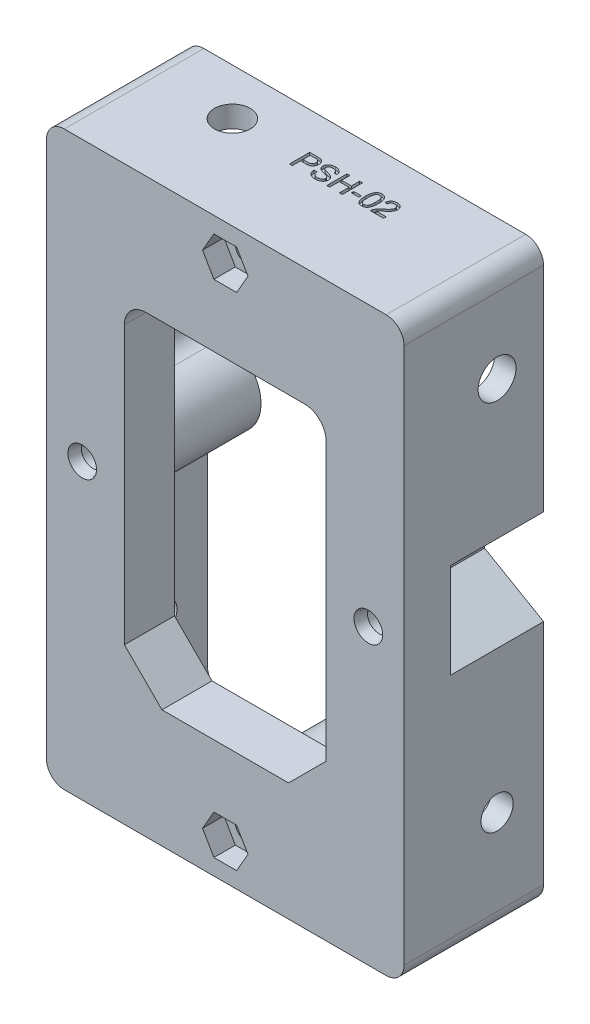
SolidWorks part; units mm, degrees
ref_plane "Front" through (0, 0, 0) normal (0, 0, 1) x (1, 0, 0)
ref_plane "Top" through (0, 0, 0) normal (0, 1, 0) x (1, 0, 0)
ref_plane "Right" through (0, 0, 0) normal (1, 0, 0) x (0, 0, -1)
sketch "Sketch3" plane through (0, 0, 0) normal (0, 0, 1) x (1, 0, 0)
  line L0 (10.9, 16.5) -> (0, 16.5) construction
  line L1 (0, 0) -> (50, 0)
  line L2 (0, 0) -> (0, 80)
  line L3 (0, 80) -> (50, 80)
  line L4 (50, 0) -> (50, 80)
  line L5 (10.9, 16.5) -> (39.1, 16.5)
  line L6 (10.9, 16.5) -> (10.9, 63.5)
  line L7 (10.9, 63.5) -> (39.1, 63.5)
  line L8 (39.1, 16.5) -> (39.1, 63.5)
  line L9 (39.1, 16.5) -> (50, 16.5) construction
  line L10 (10.9, 16.5) -> (10.9, 0) construction
  line L11 (10.9, 63.5) -> (10.9, 80) construction
  line L12 (25, 80) -> (25, 75) construction
  line L13 (25, 0) -> (25, 5) construction
  line L14 (25, 41) -> (5, 41) construction
  line L15 (25, 41) -> (45, 41) construction
  circle A0 centre (5, 41) radius 1.6 construction
  circle A1 centre (45, 41) radius 1.6 construction
  circle A2 centre (25, 5) radius 1.6
  circle A3 centre (25, 75) radius 1.6
  point P20 (0, 0)
  point P22 (25, 63.5)
  point P27 (0, 0)
  point P28 (0, 0)
  point P29 (0, 0)
  point P30 (0, 0)
  dimension "D5" = 40
  dimension "D6" = 3.2
  dimension "D1" = 50
  dimension "D2" = 80
  dimension "D3" = 28.2
  dimension "D4" = 22.5
  dimension "D7" = 24.5
  dimension "D8" = 70
extrude "Boss-Extrude1" add sketch "Sketch3" along normal blind 19.5
sketch "Sketch17" plane through (0, 0, 19.5) normal (0, 0, 1) x (1, 0, 0)
  circle A0 centre (45, 41) radius 1.6 construction
  circle A1 centre (5, 41) radius 1.6 construction
  circle A2 centre (45, 41) radius 1.6
  circle A3 centre (5, 41) radius 1.6
extrude "Cut-Extrude7" cut sketch "Sketch17" against normal through all
chamfer "Chamfer1" distance 0.4 angle 75 2 edges at (46.6, 41, 19.5) (6.6, 41, 19.5) first distance on face at (46.6, 41, 19.5)
sketch "Sketch4" plane through (0, 0, 0) normal (0, 0, -1) x (-1, 0, 0)
  line L0 (-19.8765, 3) -> (-3, 3)
  line L1 (-30.1235, 77) -> (-47, 77)
  line L4 (-47, 35.8765) -> (-47, 3)
  line L5 (-3, 46.1235) -> (-3, 77)
  line L8 (-47, 3) -> (-3, 3)
  line L9 (-3, 3) -> (-3, 77)
  line L10 (-47, 77) -> (-47, 3)
  line L11 (-3, 77) -> (-47, 77)
  line L12 (-47, 3) -> (-30.1235, 3)
  line L13 (-3, 3) -> (-3, 35.8765)
  line L14 (-47, 77) -> (-47, 46.1235)
  line L15 (-3, 77) -> (-19.8765, 77)
  arc A0 (-47, 35.8765) -> (-47, 46.1235) centre (-45, 41) ccw
  arc A1 (-3, 46.1235) -> (-3, 35.8765) centre (-5, 41) ccw
  arc A2 (-19.8765, 3) -> (-30.1235, 3) centre (-25, 5) ccw
  arc A3 (-30.1235, 77) -> (-19.8765, 77) centre (-25, 75) ccw
  circle A4 centre (-25, 75) radius 1.6 construction
  dimension "D2" = 11
  dimension "D1" = 3
extrude "Cut-Extrude1" cut sketch "Sketch4" against normal offset from surface (12.5 mm away) 7 up to face at (43, 41, 19.5)
fillet "Fillet1" radius 2.5 4 edges at (0, 0, 9.75) (50, 0, 9.75) (50, 80, 9.75) (0, 80, 9.75)
fillet "Fillet2" radius 2.5 12 edges at (3, 35.8765, 6.25) (3, 46.1235, 6.25) (47, 35.8765, 6.25) (47, 46.1235, 6.25) (47, 3, 6.25) (3, 77, 6.25) (47, 77, 6.25) (19.8765, 77, 6.25) (30.1235, 77, 6.25) (19.8765, 3, 6.25) (30.1235, 3, 6.25) (3, 3, 6.25)
sketch "Sketch5" plane through (0, 0, 0) normal (-1, 0, 0) x (0, 0, 1)
  line L1 (0, 80) -> (19.5, 80) construction
  line L2 (6.5, 67) -> (6.5, 42) construction
  line L3 (6.5, 42) -> (6.5, 14.5) construction
  line L4 (19.5, 77.5) -> (19.5, 2.5) construction
  circle A0 centre (6.5, 67) radius 2.5
  circle A2 centre (6.5, 14.5) radius 2.25
  dimension "D1" = 13
  dimension "D2" = 5
  dimension "D3" = 13
  dimension "D4" = 25
  dimension "D5" = 14.5
  dimension "D6" = 4.5
extrude "Cut-Extrude2" cut sketch "Sketch5" against normal up to next
hole_wizard "M5 Clearance Hole1" positions "Sketch6" profile "Sketch7" hole size "M5" standard "ANSI Metric" end condition up to next
sketch "Sketch6" plane through (47, 0, 0) normal (-1, 0, 0) x (0, 0, 1)
  point P0 (6.5, 67)
sketch "Sketch7" plane through (47, 67, 6.5) normal (0, 1, 0) x (0, 0, 1)
  line L0 (0, 0) -> (0, 3)
  line L1 (0, 3) -> (2.65, 3)
  line L2 (2.65, 3) -> (2.65, 0)
  line L5 (2.65, 0) -> (0, 0)
  line L11 (0, -6.35) -> (0, 107.95) construction
  dimension "Thru Hole Dia." = 5.3
  dimension "Thru Hole Depth" = 3
sketch "Sketch8" plane through (0, 80, 0) normal (0, 1, 0) x (1, 0, 0)
  line L1 (0, -19.5) -> (0, 0) construction
  line L2 (47.5, -19.5) -> (2.5, -19.5) construction
  circle A0 centre (13, -6.5) radius 2.5
  dimension "D1" = 5
  dimension "D3" = 13
  dimension "D2" = 13
extrude "Cut-Extrude3" cut sketch "Sketch8" against normal up to surface (77 mm away) up to face at (38.7422, 3, 6.25)
hole_wizard "M5 Clearance Hole2" positions "Sketch10" profile "Sketch11" hole size "M5" standard "ANSI Metric" end condition up to next
sketch "Sketch10" plane through (0, 3, 0) normal (0, 1, 0) x (1, 0, 0)
  point P0 (13, -6.5)
sketch "Sketch11" plane through (13, 3, 6.5) normal (1, 0, 0) x (0, 0, 1)
  line L0 (0, 0) -> (0, 3)
  line L1 (0, 3) -> (2.65, 3)
  line L2 (2.65, 3) -> (2.65, 0)
  line L5 (2.65, 0) -> (0, 0)
  line L11 (0, -6.35) -> (0, 107.95) construction
  dimension "Thru Hole Dia." = 5.3
  dimension "Thru Hole Depth" = 3
sketch "Sketch12" plane through (47, 0, 0) normal (-1, 0, 0) x (0, 0, 1)
  circle A0 centre (6.5, 14.5) radius 2.25 construction
  circle A1 centre (6.5, 14.5) radius 2.25
extrude "Cut-Extrude4" cut sketch "Sketch12" against normal through all
sketch "Sketch13" plane through (0, 80, 0) normal (0, 1, 0) x (1, 0, 0)
  line L0 (8, -8) -> (50, -8) construction
  line L1 (50, 0) -> (50, -19.5) construction
  line L2 (47.5, 0) -> (2.5, 0) construction
  text T0 "PSH-02"
  dimension "D1" = 8
extrude "Part Number" cut sketch "Sketch13" against normal blind 0.4
sketch "Sketch14" plane through (0, 0, 19.5) normal (0, 0, 1) x (1, 0, 0)
  line L1 (10.25, 68.5) -> (39.75, 68.5)
  line L2 (10.25, 68.5) -> (10.25, 11.5)
  line L3 (10.25, 11.5) -> (39.75, 11.5)
  line L4 (39.75, 68.5) -> (39.75, 11.5)
  line L6 (25, 68.5) -> (25, 63.5) construction
  line L7 (39.1, 63.5) -> (10.9, 63.5) construction
  line L8 (25, 11.5) -> (25, 16.5) construction
  line L9 (10.9, 16.5) -> (39.1, 16.5) construction
  dimension "D1" = 57
  dimension "D2" = 29.5
extrude "Omnicom Enlarged Socket Cavity" [suppressed] cut sketch "Sketch14" against normal through all
sketch "Sketch15" [suppressed] plane through (0, 0, 23) normal (0, 0, 1) x (1, 0, 0)
  line L0 (25, 40) -> (39.1, 40) construction
  line L1 (10, 9.5) -> (40, 9.5)
  line L2 (10, 9.5) -> (10, 70.5)
  line L3 (10, 70.5) -> (40, 70.5)
  line L4 (40, 9.5) -> (40, 70.5)
  line L5 (10, 9.5) -> (40, 70.5) construction
  line L6 (10, 70.5) -> (40, 9.5) construction
  line L7 (39.1, 16.4) -> (39.1, 63.6) construction
  line L8 (25, 40) -> (10.9, 40) construction
  line L9 (10.9, 63.6) -> (10.9, 16.4) construction
  point P0 (25, 40)
  dimension "D1" = 61
  dimension "D2" = 30
extrude "Astrodyne Enlarged Socket Cavity" [suppressed] cut sketch "Sketch15" against normal through all
sketch "Sketch16" [suppressed] plane through (0, 0, 23) normal (0, 0, 1) x (1, 0, 0)
  line L0 (25, 76) -> (25, 70.5) construction
  line L1 (40, 70.5) -> (10, 70.5) construction
  line L2 (25, 4) -> (25, 9.5) construction
  line L3 (10, 9.5) -> (40, 9.5) construction
  circle A0 centre (25, 76) radius 1.4
  circle A1 centre (25, 4) radius 1.4
  dimension "D1" = 72
  dimension "D2" = 2.8
extrude "Cut-Extrude6" [suppressed] cut sketch "Sketch16" against normal through all
chamfer "Chamfer2" [suppressed] distance 0.4 angle 70
ref_plane "Plane1" [suppressed] through (0, 0, 10) normal (0, 0, 1) x (1, 0, 0)
sketch "Sketch18" [suppressed] plane through (0, 0, 10) normal (0, 0, 1) x (1, 0, 0)
  line L0 (47, 70) -> (46.2, 70) construction
  line L1 (47, 72.65) -> (47, 67.35) construction
  line L2 (46.2, 70) -> (-6.9259, 84.235) construction
  line L3 (46.2, 70) -> (26.1844, 70) construction
  dimension "D1" = 15
  dimension "D2" = 55
  dimension "D3" = 0.8
ref_plane "Plane2" [suppressed] through (-6.9259, 84.235, 10) normal (-0.9659, 0.2588, 0) x (0, 0, 1)
sketch "Sketch19" [suppressed] plane through (-6.9259, 84.235, 10) normal (-0.9659, 0.2588, 0) x (0, 0, 1)
  line L0 (0, 0) -> (0, -5.1804) construction
  circle A0 centre (0, 0) radius 2
  dimension "D1" = 4
extrude "Cut-Extrude8" [suppressed] cut sketch "Sketch19" against normal up to surface (56.3641 mm away) up to face at (47, 67, 9.15)
chamfer "Chamfer3" distance 5.25 2 edges at (39.1, 16.5, 16) (10.9, 16.5, 16)
fillet "Fillet3" radius 3 2 edges at (39.1, 63.5, 16) (10.9, 63.5, 16)
sketch "Sketch21" plane through (0, 0, 12.5) normal (0, 0, -1) x (-1, 0, 0)
  line L1 (-42.25, 39.4123) -> (-42.25, 42.5877)
  line L2 (-42.25, 42.5877) -> (-45, 44.1754)
  line L3 (-45, 44.1754) -> (-47.75, 42.5877)
  line L4 (-47.75, 42.5877) -> (-47.75, 39.4123)
  line L5 (-47.75, 39.4123) -> (-45, 37.8246)
  line L6 (-45, 37.8246) -> (-42.25, 39.4123)
  line L7 (-7.75, 39.4123) -> (-5, 37.8246)
  line L8 (-5, 37.8246) -> (-2.25, 39.4123)
  line L9 (-2.25, 39.4123) -> (-2.25, 42.5877)
  line L10 (-2.25, 42.5877) -> (-5, 44.1754)
  line L11 (-5, 44.1754) -> (-7.75, 42.5877)
  line L12 (-7.75, 42.5877) -> (-7.75, 39.4123)
  circle A0 centre (-45, 41) radius 2.75 construction
  circle A1 centre (-5, 41) radius 2.75 construction
  dimension "D1" = 5.5
extrude "Cut-Extrude9" cut sketch "Sketch21" against normal blind 3.5 and the other way through all
sketch "Sketch23" plane through (0, 0, 0) normal (0, 0, -1) x (-1, 0, 0)
  line L0 (-42.25, 42.5877) -> (-42, 43.0207) construction
  line L4 (-45, 37.8246) -> (-42.25, 39.4123) construction
  line L5 (-42.25, 39.4123) -> (-42, 38.9793) construction
  line L6 (-50, 47.6395) -> (-50, 34.3605)
  line L7 (-42.25, 41) -> (-41.75, 41) construction
  line L8 (-42.25, 42.5877) -> (-45, 44.1754) construction
  line L9 (-42.25, 39.4123) -> (-42.25, 42.5877) construction
  line L11 (-41.75, 42.8764) -> (-50, 47.6395)
  line L12 (-41.75, 39.1236) -> (-41.75, 42.8764)
  line L13 (-50, 34.3605) -> (-41.75, 39.1236)
  line L14 (-42.25, 39.4123) -> (-42.25, 42.5877) construction
  line L15 (-50, 2.5) -> (-50, 77.5) construction
  line L17 (-25, 75) -> (-25, 5) construction
  line L18 (-7.75, 41) -> (-8.25, 41) construction
  line L21 (-7.75, 39.4123) -> (-8, 38.9793) construction
  line L22 (-7.75, 42.5877) -> (-8, 43.0207) construction
  line L23 (0, 34.3605) -> (-8.25, 39.1236)
  line L24 (-8.25, 39.1236) -> (-8.25, 42.8764)
  line L28 (-8.25, 42.8764) -> (0, 47.6395)
  line L29 (0, 47.6395) -> (0, 34.3605)
  dimension "D1" = 0.5
extrude "Cut-Extrude10" cut sketch "Sketch23" against normal offset from surface (13 mm away) 3 up to face at (45, 41, 16)
fillet "Fillet5" [suppressed] radius 2
chamfer "Chamfer5" [suppressed] distance 2 angle 45
sketch "Sketch24" plane through (0, 0, 19.5) normal (0, 0, 1) x (1, 0, 0)
  line L1 (21.8246, 75) -> (23.4123, 72.25)
  line L2 (23.4123, 72.25) -> (26.5877, 72.25)
  line L3 (26.5877, 72.25) -> (28.1754, 75)
  line L4 (28.1754, 75) -> (26.5877, 77.75)
  line L5 (26.5877, 77.75) -> (23.4123, 77.75)
  line L6 (23.4123, 77.75) -> (21.8246, 75)
  line L7 (21.8246, 5) -> (23.4123, 2.25)
  line L8 (23.4123, 2.25) -> (26.5877, 2.25)
  line L9 (26.5877, 2.25) -> (28.1754, 5)
  line L10 (28.1754, 5) -> (26.5877, 7.75)
  line L11 (26.5877, 7.75) -> (23.4123, 7.75)
  line L12 (23.4123, 7.75) -> (21.8246, 5)
  circle A0 centre (25, 75) radius 2.75 construction
  circle A1 centre (25, 5) radius 2.75 construction
  dimension "5.5" = 5.5
extrude "Cut-Extrude11" cut sketch "Sketch24" against normal blind 3
